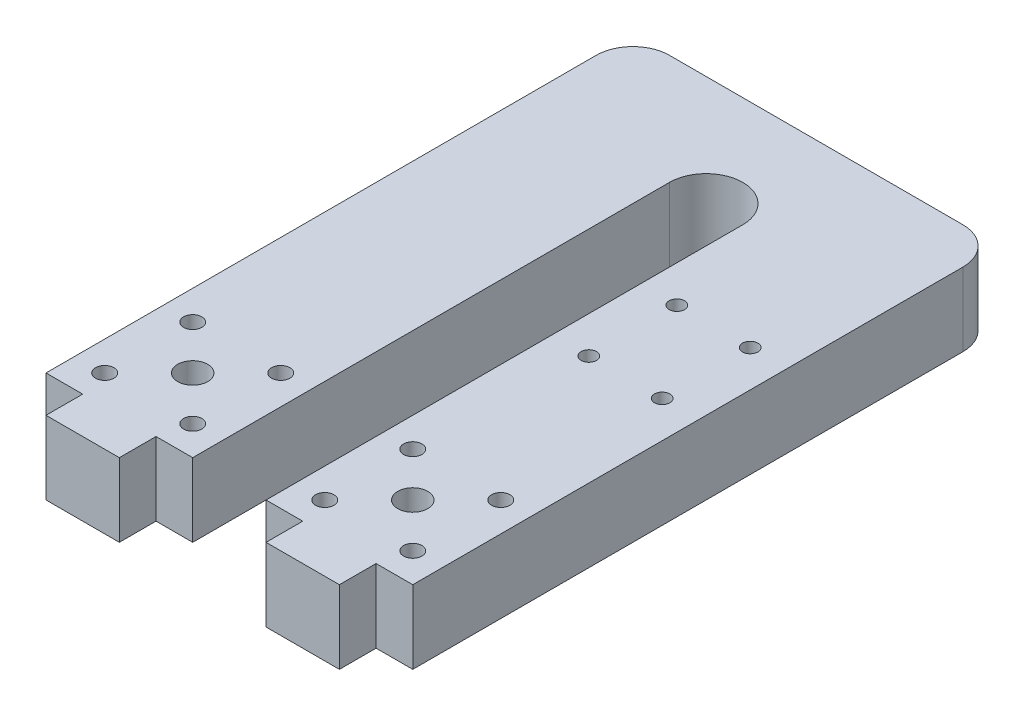
SolidWorks part; units mm, degrees
ref_plane "正面" through (0, 0, 0) normal (0, 0, 1) x (1, 0, 0)
ref_plane "平面" through (0, 0, 0) normal (0, 1, 0) x (1, 0, 0)
ref_plane "右側面" through (0, 0, 0) normal (1, 0, 0) x (0, 0, -1)
sketch "ｽｹｯﾁ1" plane through (0, 0, 0) normal (0, 1, 0) x (1, 0, 0)
  line L0 (0, 160) -> (0, 0) construction
  line L1 (-50, 0) -> (50, 0)
  line L2 (-50, 0) -> (-50, 150)
  line L3 (-40, 160) -> (40, 160)
  line L4 (50, 0) -> (50, 150)
  circle A0 centre (-30, 20) radius 4.1
  circle A1 centre (30, 20) radius 4.1
  arc A2 (40, 160) -> (50, 150) centre (40, 150) cw
  arc A3 (-50, 150) -> (-40, 160) centre (-40, 150) cw
  circle A4 centre (-42, 32) radius 2.5
  circle A5 centre (-18, 32) radius 2.5
  circle A6 centre (-18, 8) radius 2.5
  circle A7 centre (-42, 8) radius 2.5
  circle A8 centre (18, 32) radius 2.5
  circle A9 centre (18, 8) radius 2.5
  circle A10 centre (42, 8) radius 2.5
  circle A11 centre (42, 32) radius 2.5
  point P4 (0, 0)
  point P15 (50, 160)
  point P18 (-50, 160)
  dimension "D5" = 8.2
  dimension "D6" = 10
  dimension "D9" = 5
  dimension "D1" = 100
  dimension "D2" = 160
  dimension "D3" = 60
  dimension "D4" = 20
  dimension "D7" = 24
  dimension "D8" = 24
  dimension "D10" = 12
  dimension "D11" = 12
extrude "ﾎﾞｽ - 押し出し1" add sketch "ｽｹｯﾁ1" along normal blind 20
sketch "ｽｹｯﾁ2" plane through (0, 20, 0) normal (0, 1, 0) x (1, 0, 0)
  line L0 (-50, 0) -> (50, 0) construction
  line L1 (-10, 0) -> (10, 0)
  line L2 (-10, 0) -> (-10, 140)
  line L3 (-10, 140) -> (10, 140)
  line L4 (10, 0) -> (10, 140)
  line L5 (40, 160) -> (-40, 160) construction
  point P8 (0, 0)
  dimension "D1" = 20
  dimension "D2" = 20
extrude "ｶｯﾄ - 押し出し1" cut sketch "ｽｹｯﾁ2" against normal through all
fillet "ﾌｨﾚｯﾄ1" 2 edges at (-10, 10, -140) (10, 10, -140) type full round first side face at (-10, 10, -70) second side face at (10, 10, -70) middle face at (0, 10, -140)
sketch "ｽｹｯﾁ3" plane through (0, 0, 0) normal (0, 0, 1) x (1, 0, 0)
  line L0 (10, 0) -> (50, 0) construction
  line L1 (20, 0) -> (40, 0)
  line L2 (20, 0) -> (20, 20)
  line L3 (20, 20) -> (40, 20)
  line L4 (40, 0) -> (40, 20)
  line L5 (10, 20) -> (50, 20) construction
  line L6 (10, 0) -> (10, 20) construction
  line L7 (50, 20) -> (50, 0) construction
  dimension "D1" = 10
  dimension "D2" = 10
sketch "ｽｹｯﾁ4" plane through (0, 0, 0) normal (0, 0, 1) x (1, 0, 0)
  line L0 (-50, 0) -> (-10, 0) construction
  line L1 (-40, 0) -> (-20, 0)
  line L2 (-40, 0) -> (-40, 20)
  line L3 (-40, 20) -> (-20, 20)
  line L4 (-20, 0) -> (-20, 20)
  line L5 (-50, 20) -> (-10, 20) construction
  line L6 (-50, 20) -> (-50, 0) construction
  line L7 (-10, 0) -> (-10, 20) construction
  dimension "D1" = 10
  dimension "D2" = 10
extrude "ﾎﾞｽ - 押し出し2" add sketch "ｽｹｯﾁ3" along normal blind 10
extrude "ﾎﾞｽ - 押し出し3" add sketch "ｽｹｯﾁ4" along normal blind 10
sketch "ｽｹｯﾁ5" plane through (0, 20, 0) normal (0, 1, 0) x (1, 0, 0)
  line L0 (20, 102) -> (40, 78) construction
  line L1 (20, 78) -> (40, 102) construction
  line L2 (10, 0) -> (10, 130) construction
  circle A0 centre (20, 102) radius 2.1
  circle A1 centre (40, 102) radius 2.1
  circle A2 centre (20, 78) radius 2.1
  circle A3 centre (40, 78) radius 2.1
  arc A4 (10, 130) -> (-10, 130) centre (0, 130) ccw construction
  point P10 (30, 90)
  point P14 (0, 140)
  dimension "D1" = 4.2
  dimension "D2" = 20
  dimension "D3" = 24
  dimension "D4" = 20
  dimension "D5" = 50
extrude "ｶｯﾄ - 押し出し2" cut sketch "ｽｹｯﾁ5" against normal through all
